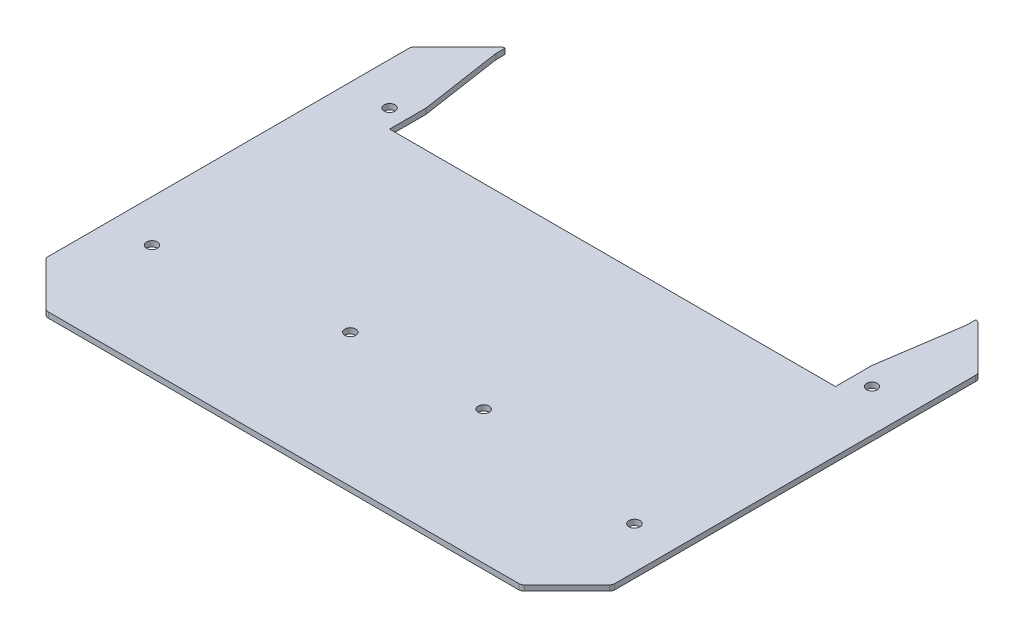
SolidWorks part; units mm, degrees
ref_plane "Plan de face" through (0, 0, 0) normal (0, 0, 1) x (1, 0, 0)
ref_plane "Plan de dessus" through (0, 0, 0) normal (0, 1, 0) x (1, 0, 0)
ref_plane "Plan de droite" through (0, 0, 0) normal (1, 0, 0) x (0, 0, -1)
sketch "Esquisse1" plane through (0, 0, 0) normal (0, 1, 0) x (1, 0, 0)
  line L0 (0, 125) -> (0, -125) construction
  line L1 (-155, 0) -> (155, 0) construction
  line L2 (-130, 125) -> (130, 125)
  line L3 (-130, -125) -> (130, -125)
  line L4 (-155, 100) -> (-155, -100)
  line L5 (155, 100) -> (155, -100)
  line L6 (-155, 100) -> (-130, 125)
  line L7 (-155, -100) -> (-130, -125)
  line L8 (130, -125) -> (155, -100)
  line L9 (130, 125) -> (155, 100)
  point P3 (0, 0)
  point P6 (0, 0)
  point P8 (0, 125)
  point P11 (0, -125)
  point P14 (-155, 0)
  point P17 (155, 0)
  dimension "D1" = 310
  dimension "D2" = 250
  dimension "D3" = 135
  dimension "D4" = 260
  dimension "D5" = 200
extrude "Boss.-Extru.1" add sketch "Esquisse1" along normal blind 3
fillet "Congé1" radius 3 8 edges at (-130, 1.5, 125) (-155, 1.5, 100) (130, 1.5, 125) (155, 1.5, 100) (155, 1.5, -100) (130, 1.5, -125) (-130, 1.5, -125) (-155, 1.5, -100)
sketch "Esquisse2" plane through (0, 3, 0) normal (0, 1, 0) x (1, 0, 0)
  line L0 (0, 125) -> (0, -125) construction
  line L1 (128.7574, 125) -> (-128.7574, 125) construction
  line L2 (-128.7574, -125) -> (128.7574, -125) construction
  line L3 (-155, 0) -> (155, 0) construction
  line L4 (-155, 98.7574) -> (-155, -98.7574) construction
  line L5 (155, -98.7574) -> (155, 98.7574) construction
  line L6 (-132, 65) -> (-132, 0) construction
  line L7 (-132, 65) -> (-155, 65) construction
  circle A0 centre (-132, 65) radius 3
  circle A1 centre (-132, -65) radius 3
  circle A2 centre (132, -65) radius 3
  circle A3 centre (132, 65) radius 3
  dimension "D1" = 6
  dimension "D2" = 23
  dimension "D3" = 65
extrude "Perçage Profilé" cut sketch "Esquisse2" against normal through all
sketch "Esquisse3" plane through (0, 3, 0) normal (0, 1, 0) x (1, 0, 0)
  line L0 (0, -125) -> (0, -52) construction
  line L1 (-128.7574, -125) -> (128.7574, -125) construction
  line L2 (-36.5, -52) -> (36.5, -52) construction
  circle A0 centre (-36.5, -52) radius 3
  circle A1 centre (36.5, -52) radius 3
  point P8 (0, -52)
  dimension "D1" = 6
  dimension "D2" = 73
  dimension "D3" = 73
extrude "Enlèv. mat.-Extru.1" cut sketch "Esquisse3" against normal through all
sketch "Esquisse4" plane through (0, 3, 0) normal (0, 1, 0) x (1, 0, 0)
  line L0 (122, 55) -> (-122, 55)
  line L1 (-122, 55) -> (-122, 75)
  line L3 (-128.7574, 125) -> (128.7574, 125)
  line L5 (122, 75) -> (122, 55)
  line L6 (155, -98.7574) -> (155, 98.7574) construction
  line L7 (0, 55) -> (0, 125) construction
  line L8 (128.7574, 125) -> (128.7574, 120)
  line L9 (128.7574, 120) -> (122, 75)
  line L10 (-128.7574, 125) -> (-128.7574, 120)
  line L11 (-128.7574, 120) -> (-122, 75)
  dimension "D1" = 33
  dimension "D2" = 70
  dimension "D3" = 20
  dimension "D4" = 5
extrude "Enlèv. mat.-Extru.2" cut sketch "Esquisse4" against normal up to next
